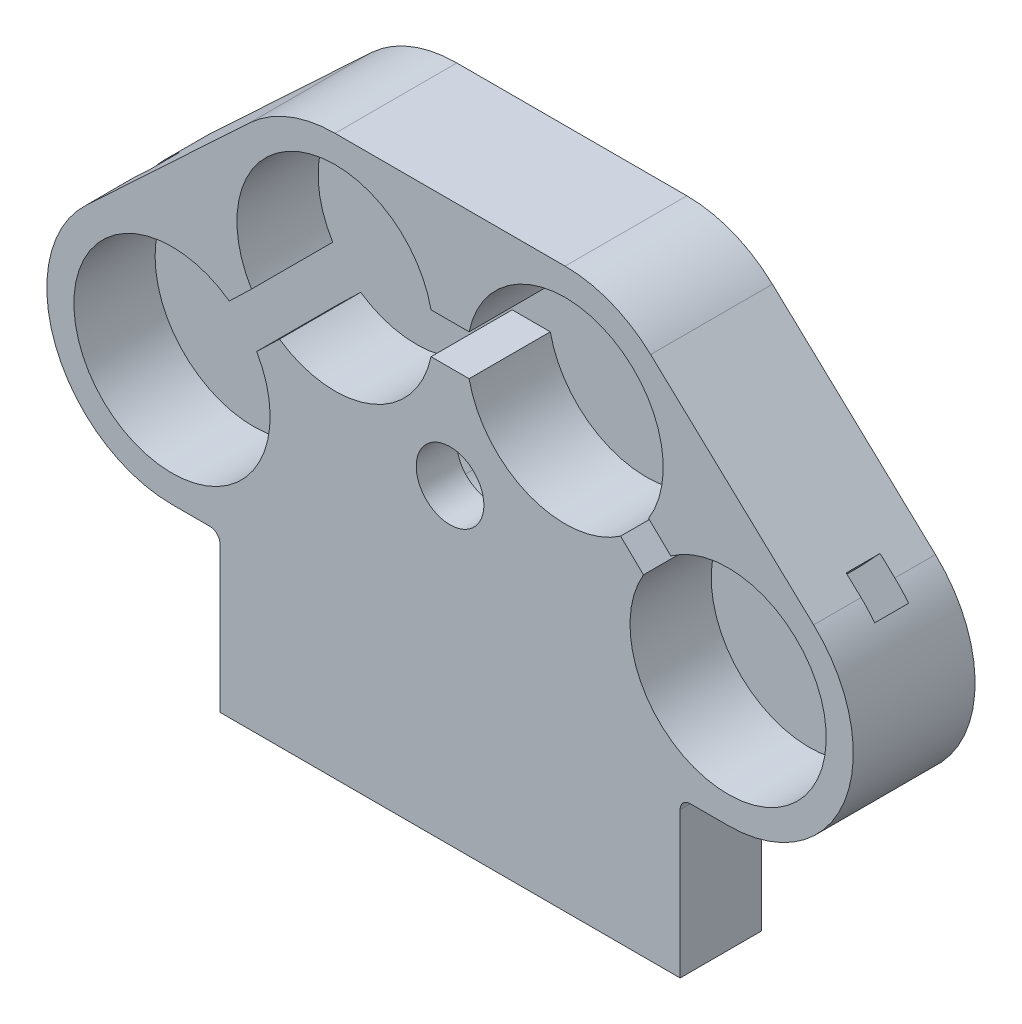
SolidWorks part; units mm, degrees
ref_plane "Front Plane" through (0, 0, 0) normal (0, 0, 1) x (1, 0, 0)
ref_plane "Top Plane" through (0, 0, 0) normal (0, 1, 0) x (1, 0, 0)
ref_plane "Right Plane" through (0, 0, 0) normal (1, 0, 0) x (0, 0, -1)
sketch "Sketch1" plane through (0, 0, 0) normal (0, 0, 1) x (1, 0, 0)
  line L0 (-11.9595, 12.7758) -> (-50.7466, -23.5332) construction
  line L1 (11.9595, 12.7758) -> (50.7466, -23.5332) construction
  line L2 (-11.9595, 12.7758) -> (11.9595, 12.7758) construction
  line L3 (-50.7466, -23.5332) -> (50.7466, -23.5332) construction
  line L4 (-17.5, -2) -> (17.5, -2) construction
  line L5 (0, 0) -> (0, -2) construction
  line L6 (-17.5, -2) -> (-17.5, 4) construction
  line L7 (-17.5, 4) -> (-20.5, 4) construction
  line L8 (-20.5, 4) -> (-20.5, -5) construction
  line L9 (-20.5, -5) -> (20.5, -5) construction
  line L10 (20.5, -5) -> (20.5, 4) construction
  line L11 (20.5, 4) -> (17.5, 4) construction
  line L12 (17.5, 4) -> (17.5, -2) construction
  line L13 (0, -2) -> (0, 40.1846) construction
  line L14 (-20.5457, 18.7784) -> (-8.5, 30.0545) construction
  line L15 (-26.8672, 25.5313) -> (-14.8215, 36.8074)
  line L16 (-20.5457, 9.5284) -> (-17.75, 9.5284)
  line L17 (-17, 8.7784) -> (-17, -2)
  line L18 (-17, -2) -> (0, -2)
  line L19 (-8.5, 39.3045) -> (0, 39.3045)
  line L20 (0, 39.3045) -> (0, -2)
  circle A0 centre (0, 0) radius 17.5 construction
  circle A1 centre (-20.5457, 18.7784) radius 7.25
  circle A2 centre (-8.5, 30.0545) radius 7.25
  circle A3 centre (-8.5, 30.0545) radius 9.25 construction
  circle A4 centre (-20.5457, 18.7784) radius 9.25 construction
  arc A5 (-17.75, 9.5284) -> (-17, 8.7784) centre (-17.75, 8.7784) cw
  arc A6 (-14.8215, 36.8074) -> (-8.5, 39.3045) centre (-8.5, 30.0545) cw
  arc A7 (-20.5457, 9.5284) -> (-26.8672, 25.5313) centre (-20.5457, 18.7784) cw
  point P31 (0, 0)
  dimension "D1" = 35
  dimension "D8" = 14.5
  dimension "D10" = 2
  dimension "D11" = 2
  dimension "D13" = 0.75
  dimension "D2" = 93.78
  dimension "D3" = 35
  dimension "2" = 2
  dimension "D4" = 6
  dimension "D5" = 3
  dimension "D6" = 3
  dimension "D7" = 3
  dimension "D9" = 17
  dimension "D12" = 0.5
extrude "Boss-Extrude1" add sketch "Sketch1" along normal blind 5 contours A7 L16 A5 L17 L18 L20 L19 A6 L15 A2 A1 region at (-10.2778, 15.5323, 0)
mirror "Mirror1" about plane through (0, 0, 0) normal (1, 0, 0) of "Boss-Extrude1"
sketch "Sketch3" plane through (0, 0, 0) normal (0, 0, -1) x (-1, 0, 0)
  line L0 (26.8672, 25.5313) -> (14.8215, 36.8074) construction
  line L1 (26.8672, 25.5313) -> (14.8215, 36.8074)
  line L2 (8.5, 39.3045) -> (-8.5, 39.3045) construction
  line L3 (8.5, 39.3045) -> (-8.5, 39.3045)
  line L4 (-26.8672, 25.5313) -> (-14.8215, 36.8074) construction
  line L5 (-26.8672, 25.5313) -> (-14.8215, 36.8074)
  line L6 (-14.2242, 12.0255) -> (-2.1785, 23.3016)
  line L7 (14.2242, 12.0255) -> (2.1785, 23.3016)
  line L8 (-2.1785, 23.3016) -> (-1.3668, 24.0615)
  line L9 (1.3668, 24.0615) -> (2.1785, 23.3016)
  arc A0 (20.5457, 9.5284) -> (26.8672, 25.5313) centre (20.5457, 18.7784) ccw construction
  arc A1 (20.5457, 9.5284) -> (26.8672, 25.5313) centre (20.5457, 18.7784) ccw construction
  arc A2 (14.8215, 36.8074) -> (8.5, 39.3045) centre (8.5, 30.0545) ccw construction
  arc A3 (14.8215, 36.8074) -> (8.5, 39.3045) centre (8.5, 30.0545) ccw
  arc A4 (-8.5, 39.3045) -> (-14.8215, 36.8074) centre (-8.5, 30.0545) ccw construction
  arc A5 (-8.5, 39.3045) -> (-14.8215, 36.8074) centre (-8.5, 30.0545) ccw
  arc A6 (-26.8672, 25.5313) -> (-20.5457, 9.5284) centre (-20.5457, 18.7784) ccw construction
  arc A7 (-26.8672, 25.5313) -> (-20.5457, 9.5284) centre (-20.5457, 18.7784) ccw construction
  circle A8 centre (-20.5457, 18.7784) radius 9.25 construction
  circle A9 centre (-8.5, 30.0545) radius 9.25 construction
  circle A10 centre (8.5, 30.0545) radius 9.25 construction
  circle A11 centre (20.5457, 18.7784) radius 9.25 construction
  circle A12 centre (0, 20.9744) radius 3.1878 construction
  arc A13 (-2.1785, 23.3016) -> (2.1785, 23.3016) centre (0, 20.9744) cw construction
  arc A14 (-26.8672, 25.5313) -> (-14.2242, 12.0255) centre (-20.5457, 18.7784) ccw
  arc A15 (26.8672, 25.5313) -> (14.2242, 12.0255) centre (20.5457, 18.7784) cw
  arc A16 (-1.3668, 24.0615) -> (1.3668, 24.0615) centre (0, 22.6014) cw
  arc M9 (20.5457, 9.5284) -> (26.8672, 25.5313) centre (20.5457, 18.7784) ccw
  line M10 (26.8672, 25.5313) -> (14.8215, 36.8074)
  arc M11 (14.8215, 36.8074) -> (8.5, 39.3045) centre (8.5, 30.0545) ccw
  line M12 (8.5, 39.3045) -> (-8.5, 39.3045)
  arc M13 (-8.5, 39.3045) -> (-14.8215, 36.8074) centre (-8.5, 30.0545) ccw
  line M14 (-14.8215, 36.8074) -> (-26.8672, 25.5313)
  arc M15 (-26.8672, 25.5313) -> (-20.5457, 9.5284) centre (-20.5457, 18.7784) ccw
  circle M23 centre (8.5, 30.0545) radius 7.25
  circle M24 centre (20.5457, 18.7784) radius 7.25
  circle M25 centre (-8.5, 30.0545) radius 7.25
  circle M26 centre (-20.5457, 18.7784) radius 7.25
  dimension "D1" = 2
extrude "Boss-Extrude2" add sketch "Sketch3" along normal blind 3 contours A15 A14 L6 A13 L7 M9 M10 M11 M12 M13 M14 M15 M23 M25 M26 M24 | M26 | M25 | M23 | M24 region at (0, 25.0337, 0) region at (-8.5, 30.0545, 0) region at (-20.5457, 18.7784, 0) region at (8.5, 30.0545, 0) region at (20.5457, 18.7784, 0)
sketch "Sketch4" plane through (0, 0, 0) normal (0, 0, 1) x (1, 0, 0)
  circle A0 centre (20.5457, 18.7784) radius 7.25 construction
  circle A1 centre (8.5, 30.0545) radius 7.25 construction
  circle A2 centre (-8.5, 30.0545) radius 7.25 construction
  circle A3 centre (-20.5457, 18.7784) radius 7.25 construction
  circle A4 centre (20.5457, 18.7784) radius 7.25
  circle A5 centre (8.5, 30.0545) radius 7.25
  circle A6 centre (-8.5, 30.0545) radius 7.25
  circle A7 centre (-20.5457, 18.7784) radius 7.25
extrude "Cut-Extrude1" [suppressed] cut sketch "Sketch4" against normal blind 1
sketch "Sketch5" plane through (0, 0, 5) normal (0, 0, 1) x (1, 0, 0)
  line L0 (-20.5457, 18.7784) -> (-8.5, 30.0545) construction
  line L1 (-11.8759, 28.9487) -> (-26.0736, 15.2364)
  line L2 (-26.0736, 15.2364) -> (-23.9895, 13.0785)
  line L3 (-23.9895, 13.0785) -> (-9.7918, 26.7908)
  line L4 (-9.7918, 26.7908) -> (-11.8759, 28.9487)
  line L5 (0, 0) -> (0, 28.253) construction
  line L6 (-8.5, 30.0545) -> (8.5, 30.0545) construction
  line L7 (-6.9065, 31.5545) -> (8.5226, 31.5545)
  line L8 (8.5226, 31.5545) -> (8.5226, 28.5545)
  line L9 (8.5226, 28.5545) -> (-6.9065, 28.5545)
  line L10 (-6.9065, 28.5545) -> (-6.9065, 31.5545)
  line L11 (23.9895, 13.0785) -> (9.7918, 26.7908)
  line L12 (26.0736, 15.2364) -> (23.9895, 13.0785)
  line L13 (11.8759, 28.9487) -> (26.0736, 15.2364)
  line L14 (9.7918, 26.7908) -> (11.8759, 28.9487)
  point P6 (-10.8338, 27.8698)
  point P16 (-6.9065, 30.0545)
  point P23 (-38.1252, 0)
  point P24 (-38.1252, 0)
  point P25 (-38.1252, 0)
  point P26 (0, 0)
  point P27 (0, 0)
  dimension "D1" = 3
  dimension "D2" = 3
extrude "Cut-Extrude2" cut sketch "Sketch5" against normal up to surface (5 mm away) up to face at (-13.2957, 18.7784, 0)
sketch "Sketch6" [suppressed] plane through (-25.9692, 27.7416, 0) normal (-0.6834, 0.73, 0) x (0.73, 0.6834, 0)
  line L0 (-16.9271, 1) -> (-1.556, 1) construction
  line L1 (-16.9271, 1) -> (-1.556, 1) construction
  line L2 (-9.1771, -5) -> (-9.1771, 4) construction
  line L3 (-7.6771, 1) -> (-10.6771, 1)
  line L4 (-7.6771, 1) -> (-7.6771, -1.5)
  line L5 (-7.6771, -1.5) -> (-10.6771, -1.5)
  line L6 (-10.6771, 1) -> (-10.6771, -1.5)
  point P8 (-9.1771, 1)
  dimension "D1" = 2.5
  dimension "D2" = 3
extrude "Cut-Extrude3" [suppressed] cut sketch "Sketch6" against normal blind 11
mirror "Mirror2" [suppressed] about plane through (0, 0, 0) normal (1, 0, 0)
sketch "Sketch7" plane through (-25.2858, 27.0116, 0) normal (-0.6834, 0.73, 0) x (0.73, 0.6834, 0)
  line L0 (-9.4161, 0) -> (4.9468, 0) construction
  line L1 (-0.6661, 0) -> (-3.6661, 0)
  line L2 (-0.6661, 0) -> (-0.6661, -2.5)
  line L3 (-0.6661, -2.5) -> (-3.6661, -2.5)
  line L4 (-3.6661, 0) -> (-3.6661, -2.5)
  line L5 (-9.4161, 0) -> (4.9468, 0) construction
  line L8 (-2.1661, -5) -> (-2.1661, 3) construction
  point P6 (-7.4615, 0)
  point P9 (-2.1661, -2.5)
  dimension "D1" = 3
  dimension "D2" = 2.5
extrude "Cut-Extrude4" cut sketch "Sketch7" against normal blind 10
mirror "Mirror3" about plane through (0, 0, 0) normal (1, 0, 0) of "Cut-Extrude4"
sketch "Sketch8" plane through (0, 0, 5) normal (0, 0, 1) x (1, 0, 0)
  circle A2 centre (0, 21) radius 3.75 construction
  circle A3 centre (0, 21) radius 2.5
  dimension "D1" = 7.5
  dimension "D2" = 5
  dimension "D3" = 21
extrude "Cut-Extrude5" cut sketch "Sketch8" against normal blind 10
sketch "Sketch9" plane through (0, 0, 0) normal (0, 0, -1) x (-1, 0, 0)
  line L0 (1.3668, 24.0615) -> (14.2242, 12.0255) construction
  line L1 (-14.2242, 12.0255) -> (-1.3668, 24.0615) construction
  line L2 (1.3668, 24.0615) -> (14.2242, 12.0255) construction
  line L3 (-14.2242, 12.0255) -> (-1.3668, 24.0615) construction
  line L4 (-1.3668, 24.0615) -> (-4.9947, 20.6654)
  line L5 (-4.9947, 20.6654) -> (-1.3668, 24.0615)
  line L6 (0, 21) -> (0, 24.6014) construction
  line L7 (1.3668, 24.0615) -> (4.9947, 20.6654)
  line L8 (-4.9947, 20.6654) -> (-2.8289, 18.3518)
  line L9 (4.9947, 20.6654) -> (2.8289, 18.3518)
  arc A0 (1.3668, 24.0615) -> (-1.3668, 24.0615) centre (0, 22.6014) ccw construction
  arc A1 (1.3668, 24.0615) -> (-1.3668, 24.0615) centre (0, 22.6014) ccw
  circle A2 centre (0, 21) radius 3.875 construction
  arc A3 (-2.8289, 18.3518) -> (2.8289, 18.3518) centre (0, 21) ccw
  point P14 (2.7849, 18.3056)
  circle M6 centre (0, 21) radius 2.5
  line M16 (14.2242, 12.0255) -> (1.3668, 24.0615)
  arc M17 (1.3668, 24.0615) -> (-1.3668, 24.0615) centre (0, 22.6014) ccw
  line M18 (-1.3668, 24.0615) -> (-14.2242, 12.0255)
  dimension "D1" = 7.75
extrude "Cut-Extrude6" cut sketch "Sketch9" against normal blind 3 contours M16 M17 M18 M6 | M6 region at (0, 24.4766, 0) region at (0, 21, 0)
sketch "Sketch10" plane through (0, 0, 5) normal (0, 0, 1) x (1, 0, 0)
  line L0 (-14.2913, 22.4451) -> (-12.6021, 24.0766) construction
  line L1 (-14.2913, 22.4451) -> (-12.6021, 24.0766)
  line L8 (-20.5457, 9.5284) -> (-17.75, 9.5284)
  line L9 (-17, 8.7784) -> (-17, -2)
  line L10 (-17, -2) -> (17, -2)
  line L11 (17, -2) -> (17, 8.7784)
  line L12 (17.75, 9.5284) -> (20.5457, 9.5284)
  line L13 (26.8672, 25.5313) -> (14.8215, 36.8074)
  line L14 (8.5, 39.3045) -> (-8.5, 39.3045)
  line L15 (-14.8215, 36.8074) -> (-26.8672, 25.5313)
  line L16 (-20.5457, 9.5284) -> (-17.75, 9.5284)
  line L17 (-17, 8.7784) -> (-17, -2)
  line L18 (-17, -2) -> (17, -2)
  line L19 (17, -2) -> (17, 8.7784)
  line L20 (17.75, 9.5284) -> (20.5457, 9.5284)
  line L21 (26.8672, 25.5313) -> (14.8215, 36.8074)
  line L22 (8.5, 39.3045) -> (-8.5, 39.3045)
  line L23 (-14.8215, 36.8074) -> (-26.8672, 25.5313)
  line L28 (26.4882, 22.9316) -> (27.8786, 24.4168)
  line L29 (26.8672, 25.5313) -> (25.7721, 26.5564)
  line L30 (25.7721, 26.5564) -> (24.2981, 24.9818)
  line L31 (16.3123, 24.664) -> (14.671, 26.2491)
  line L32 (1.4069, 31.5545) -> (-1.4069, 31.5545)
  line L33 (-14.671, 26.2491) -> (-16.3123, 24.664)
  line L34 (-24.2981, 24.9818) -> (-25.7721, 26.5564)
  line L35 (-25.7721, 26.5564) -> (-26.8672, 25.5313)
  line L36 (-27.8786, 24.4168) -> (-26.4882, 22.9316)
  line L37 (-14.2913, 22.4451) -> (-12.6021, 24.0766)
  line L38 (-1.4069, 28.5545) -> (1.4069, 28.5545)
  line L39 (12.6021, 24.0766) -> (14.2913, 22.4451)
  line L41 (26.8672, 25.5313) -> (25.7721, 26.5564)
  line L43 (16.3123, 24.664) -> (14.671, 26.2491)
  line L44 (1.4069, 31.5545) -> (-1.4069, 31.5545)
  line L45 (-14.671, 26.2491) -> (-16.3123, 24.664)
  line L47 (-25.7721, 26.5564) -> (-26.8672, 25.5313)
  line L49 (-14.2913, 22.4451) -> (-12.6021, 24.0766)
  line L50 (-1.4069, 28.5545) -> (1.4069, 28.5545)
  line L51 (12.6021, 24.0766) -> (14.2913, 22.4451)
  arc A0 (-16.3123, 24.664) -> (-14.2913, 22.4451) centre (-20.5457, 18.7784) ccw construction
  arc A1 (-16.3123, 24.664) -> (-14.2913, 22.4451) centre (-20.5457, 18.7784) ccw
  arc A2 (14.2913, 22.4451) -> (16.3123, 24.664) centre (20.5457, 18.7784) ccw construction
  arc A3 (14.2913, 22.4451) -> (16.3123, 24.664) centre (20.5457, 18.7784) ccw
  arc A6 (-26.8672, 25.5313) -> (-20.5457, 9.5284) centre (-20.5457, 18.7784) ccw
  arc A7 (-17, 8.7784) -> (-17.75, 9.5284) centre (-17.75, 8.7784) ccw
  arc A8 (17.75, 9.5284) -> (17, 8.7784) centre (17.75, 8.7784) ccw
  arc A9 (20.5457, 9.5284) -> (26.8672, 25.5313) centre (20.5457, 18.7784) ccw
  arc A10 (14.8215, 36.8074) -> (8.5, 39.3045) centre (8.5, 30.0545) ccw
  arc A11 (-8.5, 39.3045) -> (-14.8215, 36.8074) centre (-8.5, 30.0545) ccw
  arc A12 (-26.8672, 25.5313) -> (-20.5457, 9.5284) centre (-20.5457, 18.7784) ccw
  arc A13 (-17, 8.7784) -> (-17.75, 9.5284) centre (-17.75, 8.7784) ccw
  arc A14 (17.75, 9.5284) -> (17, 8.7784) centre (17.75, 8.7784) ccw
  arc A15 (20.5457, 9.5284) -> (26.8672, 25.5313) centre (20.5457, 18.7784) ccw
  arc A16 (14.8215, 36.8074) -> (8.5, 39.3045) centre (8.5, 30.0545) ccw
  arc A17 (-8.5, 39.3045) -> (-14.8215, 36.8074) centre (-8.5, 30.0545) ccw
  arc A22 (14.2913, 22.4451) -> (26.4882, 22.9316) centre (20.5457, 18.7784) ccw
  arc A23 (27.8786, 24.4168) -> (26.8672, 25.5313) centre (20.5457, 18.7784) ccw
  arc A24 (24.2981, 24.9818) -> (16.3123, 24.664) centre (20.5457, 18.7784) ccw
  arc A25 (14.671, 26.2491) -> (1.4069, 31.5545) centre (8.5, 30.0545) ccw
  arc A26 (-1.4069, 31.5545) -> (-14.671, 26.2491) centre (-8.5, 30.0545) ccw
  arc A27 (-16.3123, 24.664) -> (-24.2981, 24.9818) centre (-20.5457, 18.7784) ccw
  arc A28 (-26.8672, 25.5313) -> (-27.8786, 24.4168) centre (-20.5457, 18.7784) ccw
  arc A29 (-26.4882, 22.9316) -> (-14.2913, 22.4451) centre (-20.5457, 18.7784) ccw
  arc A30 (-12.6021, 24.0766) -> (-1.4069, 28.5545) centre (-8.5, 30.0545) ccw
  arc A31 (1.4069, 28.5545) -> (12.6021, 24.0766) centre (8.5, 30.0545) ccw
  arc A32 (14.2913, 22.4451) -> (26.4882, 22.9316) centre (20.5457, 18.7784) ccw
  arc A33 (27.8786, 24.4168) -> (26.8672, 25.5313) centre (20.5457, 18.7784) ccw
  arc A34 (24.2981, 24.9818) -> (16.3123, 24.664) centre (20.5457, 18.7784) ccw
  arc A35 (14.671, 26.2491) -> (1.4069, 31.5545) centre (8.5, 30.0545) ccw
  arc A36 (-1.4069, 31.5545) -> (-14.671, 26.2491) centre (-8.5, 30.0545) ccw
  arc A37 (-16.3123, 24.664) -> (-24.2981, 24.9818) centre (-20.5457, 18.7784) ccw
  arc A38 (-26.8672, 25.5313) -> (-27.8786, 24.4168) centre (-20.5457, 18.7784) ccw
  arc A39 (-26.4882, 22.9316) -> (-14.2913, 22.4451) centre (-20.5457, 18.7784) ccw
  arc A40 (-12.6021, 24.0766) -> (-1.4069, 28.5545) centre (-8.5, 30.0545) ccw
  arc A41 (1.4069, 28.5545) -> (12.6021, 24.0766) centre (8.5, 30.0545) ccw
  circle M37 centre (0, 21) radius 2.5
  line M38 (-16.3123, 24.664) -> (-14.671, 26.2491)
  arc M39 (-14.671, 26.2491) -> (-1.4069, 31.5545) centre (-8.5, 30.0545) cw
  line M40 (-1.4069, 31.5545) -> (1.4069, 31.5545)
  arc M41 (1.4069, 31.5545) -> (14.671, 26.2491) centre (8.5, 30.0545) cw
  line M42 (14.671, 26.2491) -> (16.3123, 24.664)
  arc M43 (16.3123, 24.664) -> (14.2913, 22.4451) centre (20.5457, 18.7784) cw
  line M44 (14.2913, 22.4451) -> (12.6021, 24.0766)
  arc M45 (12.6021, 24.0766) -> (1.4069, 28.5545) centre (8.5, 30.0545) cw
  line M46 (1.4069, 28.5545) -> (-1.4069, 28.5545)
  arc M47 (-1.4069, 28.5545) -> (-12.6021, 24.0766) centre (-8.5, 30.0545) cw
  line M48 (-12.6021, 24.0766) -> (-14.2913, 22.4451)
  arc M49 (-14.2913, 22.4451) -> (-16.3123, 24.664) centre (-20.5457, 18.7784) cw
  arc M50 (-26.8672, 25.5313) -> (-20.5457, 9.5284) centre (-20.5457, 18.7784) ccw
  line M51 (-20.5457, 9.5284) -> (-17.75, 9.5284)
  arc M52 (-17.75, 9.5284) -> (-17, 8.7784) centre (-17.75, 8.7784) cw
  line M53 (-17, 8.7784) -> (-17, -2)
  line M54 (-17, -2) -> (17, -2)
  line M55 (17, -2) -> (17, 8.7784)
  arc M56 (17, 8.7784) -> (17.75, 9.5284) centre (17.75, 8.7784) cw
  line M57 (17.75, 9.5284) -> (20.5457, 9.5284)
  arc M58 (20.5457, 9.5284) -> (26.8672, 25.5313) centre (20.5457, 18.7784) ccw
  line M59 (26.8672, 25.5313) -> (14.8215, 36.8074)
  arc M60 (14.8215, 36.8074) -> (8.5, 39.3045) centre (8.5, 30.0545) ccw
  line M61 (8.5, 39.3045) -> (-8.5, 39.3045)
  arc M62 (-8.5, 39.3045) -> (-14.8215, 36.8074) centre (-8.5, 30.0545) ccw
  line M63 (-14.8215, 36.8074) -> (-26.8672, 25.5313)
  dimension "D1" = 0
  dimension "D2" = 0
extrude "Boss-Extrude3" add sketch "Sketch10" along normal blind 1 contours L23 A12 A15 L21 A1 A3 M63 M50 M51 M52 M53 M54 M55 M56 M57 M58 M59 M60 M61 M62 M49 M38 M39 M40 M41 M42 M43 M44 M45 M46 M47 M48 M37 region at (0, 10.7497, 5) region at (-26.1506, 24.7823, 5) region at (0, 32.6775, 5) region at (26.1506, 24.7823, 5)
